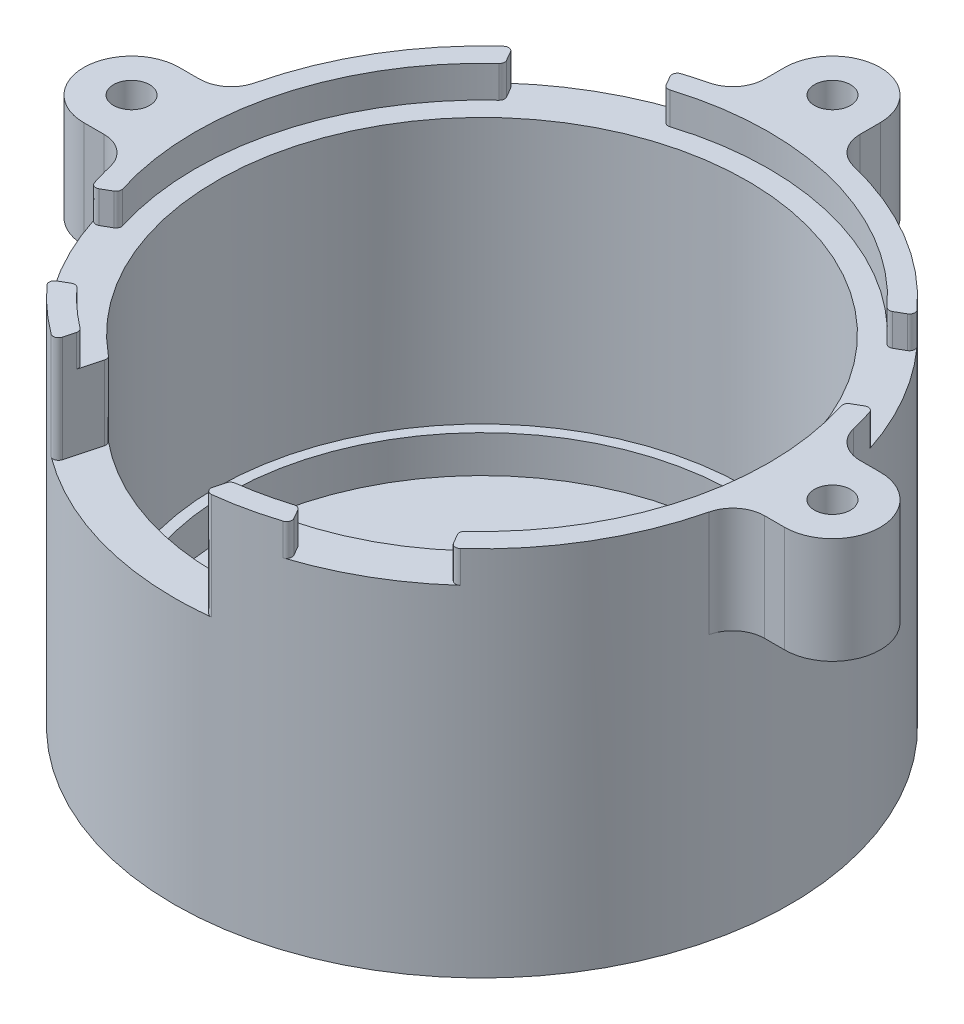
SolidWorks part; units mm, degrees
ref_plane "Plan de face" through (0, 0, 0) normal (0, 0, 1) x (1, 0, 0)
ref_plane "Plan de dessus" through (0, 0, 0) normal (0, 1, 0) x (1, 0, 0)
ref_plane "Plan de droite" through (0, 0, 0) normal (1, 0, 0) x (0, 0, -1)
sketch "Sketch1" plane through (0, 0, 0) normal (0, 0, 1) x (1, 0, 0)
  line L0 (0, 34.5752) -> (0, -31.3539) construction
  line L2 (29, -3.5) -> (29, 31.5)
  line L3 (29, 31.5) -> (27, 31.5)
  line L5 (25, 28.5) -> (25, 3.5)
  line L8 (25, 3.5) -> (24, 3.5)
  line L9 (24, 3.5) -> (24, 0)
  line L10 (24, 0) -> (9, 0)
  line L13 (29, -3.5) -> (10, -3.5)
  line L14 (25, 28.5) -> (27, 28.5)
  line L15 (27, 28.5) -> (27, 31.5)
  line L19 (10, -3.5) -> (10, -7.5)
  line L20 (10, -7.5) -> (6.5, -7.5)
  line L21 (9, 0) -> (8, -1)
  line L22 (8, -1) -> (8, -6)
  line L23 (8, -6) -> (6.5, -6)
  line L24 (6.5, -6) -> (6.5, -7.5)
  dimension "D1" = 25
  dimension "D2" = 4
  dimension "D3" = 8
  dimension "D4" = 25
  dimension "D5" = 3.5
  dimension "D6" = 1
  dimension "D7" = 4
  dimension "D8" = 2
  dimension "D9" = 3
  dimension "D10" = 1
  dimension "D11" = 5
  dimension "D12" = 10
  dimension "D13" = 1.5
  dimension "D14" = 1.5
  dimension "D16" = 24
revolve "Revolve1" add sketch "Sketch1" angle 360 about L0 region at (19.5, -3.0498, 0)
sketch "Esquisse1" plane through (0, 31.5, 0) normal (0, 1, 0) x (1, 0, 0)
  line L0 (4.5, 33) -> (4.5, 28.6487)
  line L1 (-4.5, 33) -> (-4.5, 28.6487)
  arc A0 (4.5, 33) -> (-4.5, 33) centre (0, 33) ccw
  circle A1 centre (0, 33) radius 2.4
  arc A2 (-4.5, 28.6487) -> (4.5, 28.6487) centre (0, 0) cw
  circle A3 centre (0, 0) radius 29 construction
  circle A4 centre (0, 33) radius 1.7 construction
  point P10 (0, 0)
  circle M4 centre (0, 0) radius 29
  dimension "D1" = 4.8
  dimension "D2" = 9
  dimension "D4" = 3.4
  dimension "D3" = 33
extrude "Boss.-Extru.1" add sketch "Esquisse1" against normal blind 10 contours L0 A0 L1 A1 M4 region at (4.3738, 31.5, -30.8244)
extrude "Boss.-Extru.2" add sketch "Esquisse1<3>" against normal blind 4 contours A1 A4 region at (0, 31.5, -33)
sketch "Esquisse1<3>" plane through (0, 31.5, 0) normal (0, 1, 0) x (1, 0, 0) same geometry as "Esquisse1"
chamfer "Chanfrein2" distance 0.5 angle 45 1 edges at (0, 21.5, -30.6)
fillet "Congé1" radius 3 2 edges at (4.5, 26.5, -28.6487) (-4.5, 26.5, -28.6487)
pattern_circular "Répétition circulaire1" count 4 over 360 about axis through (0, 34.5752, 0) along (0, 1, 0) skipping 2 of "Boss.-Extru.1", "Congé1", "Boss.-Extru.2", "Chanfrein2"
sketch "Esquisse4" plane through (0, 31.5, 0) normal (0, 1, 0) x (1, 0, 0)
  point P0 (0, 33)
  point P3 (33, 0)
  point P9 (-33, 0)
hole_wizard "M3 Clearance Hole1" positions "Esquisse4" profile "Esquisse3" hole size "M3" standard "ANSI Metric" end condition through all
sketch "Esquisse3" plane through (0, 31.5, -33) normal (1, 0, 0) x (0, 0, 1)
  line L0 (0, 0) -> (0, 39)
  line L1 (0, 39) -> (1.7, 39)
  line L2 (1.7, 39) -> (1.7, 0)
  line L5 (1.7, 0) -> (0, 0)
  line L11 (0, -6.35) -> (0, 107.95) construction
  dimension "Thru Hole Dia." = 3.4
  dimension "Thru Hole Depth" = 39
sketch "Esquisse5" plane through (0, 31.5, 0) normal (0, 1, 0) x (1, 0, 0)
  line L0 (0, 0) -> (0, 37.5) construction
  line L1 (0, 0) -> (7.5058, 28.0118) construction
  line L2 (0, 0) -> (25.1147, 14.5) construction
  line L3 (25.6424, 8.4538) -> (27.4089, 9.4737)
  line L4 (20.1424, 17.9801) -> (21.9089, 19)
  line L5 (21.0257, 18.49) -> (26.5257, 8.9637) construction
  line L6 (0, 0) -> (14.5, -25.1147) construction
  line L7 (8.4538, -25.6424) -> (9.4737, -27.4089)
  line L8 (18.49, -21.0257) -> (8.9637, -26.5257) construction
  line L9 (17.9801, -20.1424) -> (19, -21.9089)
  line L10 (0, 0) -> (-25.1147, -14.5) construction
  line L11 (-25.6424, -8.4538) -> (-27.4089, -9.4737)
  line L12 (-21.0257, -18.49) -> (-26.5257, -8.9637) construction
  line L13 (-20.1424, -17.9801) -> (-21.9089, -19)
  line L14 (0, 0) -> (-14.5, 25.1147) construction
  line L15 (-8.4538, 25.6424) -> (-9.4737, 27.4089)
  line L16 (-18.49, 21.0257) -> (-8.9637, 26.5257) construction
  line L17 (-17.9801, 20.1424) -> (-19, 21.9089)
  line L18 (0, 0) -> (-7.5058, -28.0118) construction
  line L19 (-15.5895, -19.544) -> (-16.7047, -23.7056)
  line L20 (3.729, -24.7203) -> (2.6139, -28.882)
  arc A0 (4.5, 33) -> (-4.5, 33) centre (0, 33) ccw construction
  arc A1 (28.1922, 6.7969) -> (6.7969, 28.1922) centre (0, 0) ccw construction
  arc A2 (-28.1922, -6.7969) -> (28.1922, -6.7969) centre (0, 0) ccw construction
  circle A3 centre (0, 0) radius 27 construction
  circle A4 centre (0, 0) radius 27 construction
  arc A5 (20.1424, 17.9801) -> (25.6424, 8.4538) centre (0, 0) cw
  arc A6 (21.9089, 19) -> (27.4089, 9.4737) centre (0, 0) cw
  arc A7 (17.9801, -20.1424) -> (8.4538, -25.6424) centre (0, 0) cw
  arc A8 (19, -21.9089) -> (9.4737, -27.4089) centre (0, 0) cw
  arc A9 (-20.1424, -17.9801) -> (-25.6424, -8.4538) centre (0, 0) cw
  arc A10 (-21.9089, -19) -> (-27.4089, -9.4737) centre (0, 0) cw
  arc A11 (-17.9801, 20.1424) -> (-8.4538, 25.6424) centre (0, 0) cw
  arc A12 (-19, 21.9089) -> (-9.4737, 27.4089) centre (0, 0) cw
  arc A14 (-16.7047, -23.7056) -> (2.6139, -28.882) centre (0, 0) ccw
  arc A15 (-15.5895, -19.544) -> (3.729, -24.7203) centre (0, 0) ccw
  circle A16 centre (0, 0) radius 25 construction
  point P21 (23.7757, 13.7269)
  point P22 (6.5784, -24.5435)
  point P46 (0, 0)
  point P54 (0, 0)
  point P55 (-15.9801, -19.6884)
  point P57 (-6.4705, -24.1481)
  circle M12 centre (0, 0) radius 27
  arc M15 (-6.7969, 28.1922) -> (-28.1922, 6.7969) centre (0, 0) ccw
  arc M27 (-28.1922, -6.7969) -> (28.1922, -6.7969) centre (0, 0) ccw
  arc M33 (28.1922, 6.7969) -> (6.7969, 28.1922) centre (0, 0) ccw
  dimension "D4" = 4
  dimension "D6" = 20
  dimension "D1" = 15
  dimension "D2" = 45
  dimension "D3" = 11
  dimension "D5" = 45
extrude "Enlèv. mat.-Extru.1" cut sketch "Esquisse5" against normal up to surface (3 mm away) contours L13 L11 M12 M27 | L9 L7 M12 M27 | L4 L3 M12 M33 | L17 L15 M12 M15 region at (24.0908, 31.5, -13.9088) region at (-13.9088, 31.5, -24.0908) region at (13.9088, 31.5, 24.0908) region at (-24.0908, 31.5, 13.9088) up to face at (0, 28.5, 27)
extrude "Enlèv. mat.-Extru.2" cut sketch "Esquisse5<3>" against normal blind 10 contours A14 L20 A15 L19
sketch "Esquisse5<3>" plane through (0, 31.5, 0) normal (0, 1, 0) x (1, 0, 0) same geometry as "Esquisse5"
fillet "Congé2" radius 0.5 22 edges at (21.9089, 30, -19) (20.1424, 30, -17.9801) (27.4089, 30, -9.4737) (25.6424, 30, -8.4538) (19, 30, 21.9089) (17.9801, 30, 20.1424) (9.4737, 30, 27.4089) (8.4538, 30, 25.6424) (-21.9089, 30, 19) (-20.1424, 30, 17.9801) (-27.4089, 30, 9.4737) (-25.6424, 30, 8.4538) (-19, 30, -21.9089) (-17.9801, 30, -20.1424) (-9.4737, 30, -27.4089) (-8.4538, 30, -25.6424) (-15.5895, 25, 19.544) (3.729, 25, 24.7203) (3.1681, 30, 26.8135) (2.6139, 26.5, 28.882) (-16.1504, 30, 21.6371) (-16.7047, 26.5, 23.7056)
